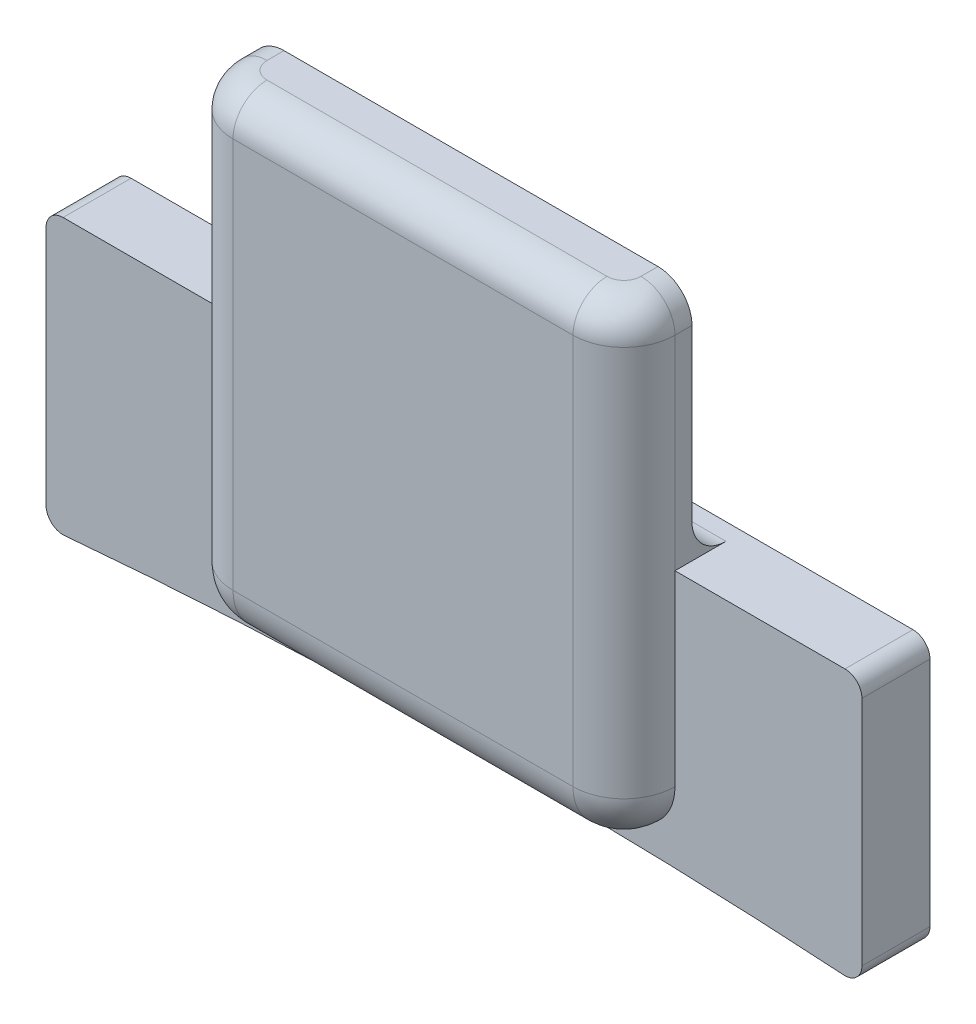
SolidWorks part; units mm, degrees
material "7079 Alloy"
ref_plane "Front Plane" through (0, 0, 0) normal (0, 0, 1) x (1, 0, 0)
ref_plane "Top Plane" through (0, 0, 0) normal (0, 1, 0) x (1, 0, 0)
ref_plane "Right Plane" through (0, 0, 0) normal (1, 0, 0) x (0, 0, -1)
ref_plane "Plane1" through (0, 0, 0) normal (0, 0, -1) x (-1, 0, 0)
sketch "Sketch1" plane through (0, 0, 0) normal (0, 0, -1) x (-1, 0, 0)
  line L0 (27.5, -16.2631) -> (27.5, 0)
  line L1 (27.5, 0) -> (-20.5, 0)
  line L2 (-20.5, 0) -> (-20.5, -15.7012)
  arc A0 (-20.5, -15.7012) -> (27.5, -16.2631) centre (0, -315) cw
  dimension "D1" = 300
  dimension "D2" = 48
extrude "Boss-Extrude1" add sketch "Sketch1" against normal blind 4
sketch "Sketch4" plane through (0, 0, 4) normal (0, 0, 1) x (1, 0, 0)
  line L0 (9.5, 0) -> (9.5, -14)
  line L1 (9.5, -14) -> (-16.5, -14)
  line L2 (-16.5, -14) -> (-16.5, 0)
  line L3 (-16.5, 0) -> (9.5, 0)
  line L5 (20.5, 0) -> (20.5, -15.7012) construction
  dimension "D1" = 26
  dimension "D2" = 11
extrude "Boss-Extrude2" add sketch "Sketch4" along normal blind 3
fillet "Fillet1" radius 1 4 edges at (20.5, 0, 2) (-27.5, 0, 2) (20.5, -15.7012, 2) (-27.5, -16.2631, 2) tangent propagation no
fillet "Fillet3" radius 3 3 edges at (-3.5, -14, 7) (-16.5, -7, 7) (9.5, -7, 7)
fillet "Fillet4" radius 3 2 edges at (-15.6213, -13.1213, 6.1213) (8.6213, -13.1213, 6.1213)
sketch "Sketch21" plane through (0, 0, 0) normal (0, 1, 0) x (1, 0, 0)
  line L0 (6.5, -7) -> (-13.5, -7)
  line L1 (-16.5, -4) -> (-16.5, -3)
  line L3 (-16.5, -3) -> (9.5, -3)
  line L4 (9.5, -3) -> (9.5, -4)
  line L5 (9.5, -4) -> (19.5, -4) construction
  arc A0 (-13.5, -7) -> (-16.5, -4) centre (-13.5, -4) cw
  arc A1 (6.5, -7) -> (9.5, -4) centre (6.5, -4) ccw construction
  arc A2 (9.5, -4) -> (6.5, -7) centre (6.5, -4) cw
  dimension "D1" = 4
extrude "Boss-Extrude9" add sketch "Sketch21" along normal blind 14
fillet "Fillet5" radius 2 5 edges at (-16.5, 14, 3.5) (-15.6213, 14, 6.1213) (9.5, 14, 3.5) (8.6213, 14, 6.1213) (-3.5, 14, 7)
fillet "Fillet6" radius 2 1 edges at (-3.5, 0, 3)
fillet "Fillet7" [suppressed] radius 2
